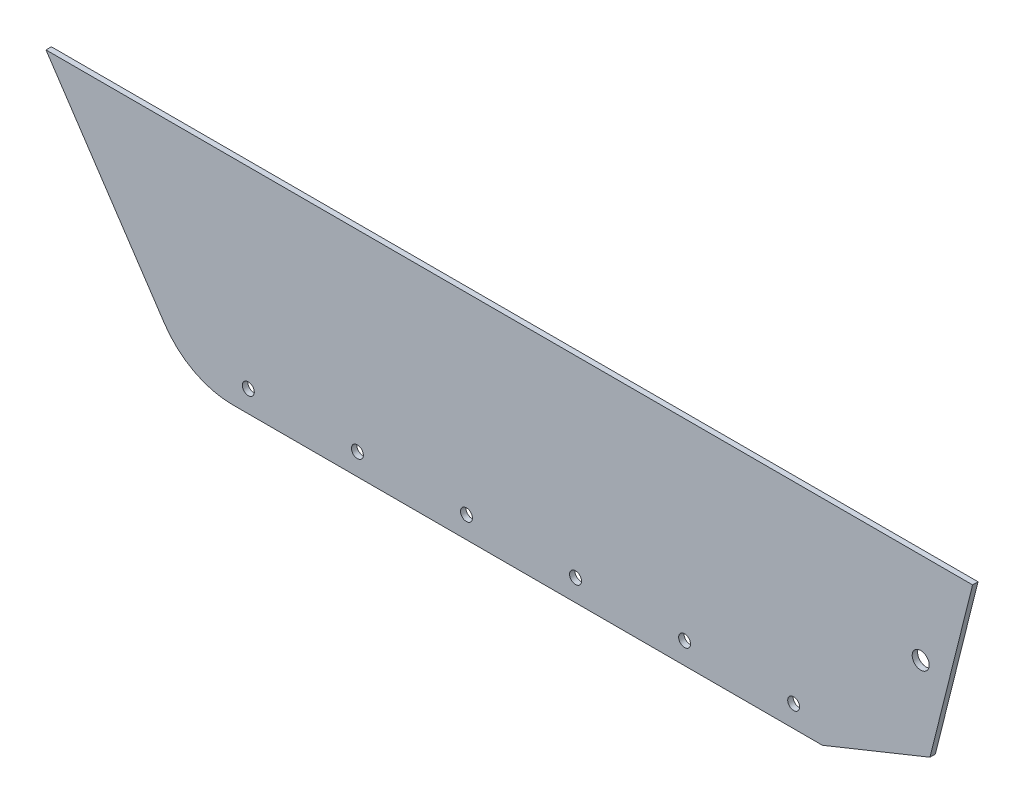
SolidWorks part; units mm, degrees
material "5052-H34"
ref_plane "Front Plane" through (0, 0, 0) normal (0, 0, 1) x (1, 0, 0)
ref_plane "Top Plane" through (0, 0, 0) normal (0, 1, 0) x (1, 0, 0)
ref_plane "Right Plane" through (0, 0, 0) normal (1, 0, 0) x (0, 0, -1)
sketch "Sketch1" plane through (0, 0, 0) normal (0, 0, 1) x (1, 0, 0)
  line L6 (-98.8794, 3.851) -> (-31.8794, -96.649)
  line L7 (428.1206, 28.9396) -> (403.1206, -71.149)
  line L9 (403.1206, -71.149) -> (366, -96.649)
  line L10 (-31.8794, -96.649) -> (366, -96.649)
  line L12 (-98.8794, 3.851) -> (-115.6052, 28.9396)
  line L13 (-115.6052, 28.9396) -> (428.1206, 28.9396)
  circle A0 centre (3.1206, -83.899) radius 3.5
  circle A1 centre (67.1206, -83.899) radius 3.5
  circle A2 centre (131.1206, -83.899) radius 3.5
  circle A3 centre (195.1206, -83.899) radius 3.5
  circle A4 centre (259.1206, -83.899) radius 3.5
  circle A5 centre (323.1206, -83.899) radius 3.5
  point P0 (-48.8794, -71.149)
  point P2 (-31.8794, -96.649)
  point P8 (48, -83.899)
  point P9 (403.1206, -71.149)
  dimension "D2" = 64
  dimension "D4" = 64
  dimension "D14" = 7
  dimension "D1" = 25.5
  dimension "D3" = 75
  dimension "D5" = 25
  dimension "D6" = 80
  dimension "D7" = 527
  dimension "D8" = 180
  dimension "D9" = 64
  dimension "D10" = 64
  dimension "D11" = 64
  dimension "D12" = 123.69
  dimension "D13" = 12.75
  dimension "D15" = 366
  dimension "D16" = 115.6052
extrude "Boss-Extrude1" add sketch "Sketch1" along normal blind 3.175 contours L12 L13 L7 L9 L10 L6
extrude "Cut-Extrude1" cut sketch "Sketch1<4>" along normal through all contours A0 | A1 | A2 | A3 | A4 | A5 region at (3.1206, -83.899, 0)
sketch "Sketch1<4>" plane through (0, 0, 0) normal (0, 0, 1) x (1, 0, 0) same geometry as "Sketch1"
sketch "Sketch2" plane through (0, 0, 0) normal (0, 0, -1) x (-1, 0, 0)
  circle A0 centre (-291.1206, -83.899) radius 6.5
  circle A2 centre (-241.5603, -124.3932) radius 6.5
  circle A3 centre (-192, -83.899) radius 6.5
  circle A4 centre (-128, -83.899) radius 6.5
  circle A5 centre (-64, -83.899) radius 6.5
  circle A6 centre (0, -83.899) radius 6.5
  dimension "D2" = 0
  dimension "D3" = 64
  dimension "D4" = 64
  dimension "D5" = 64
  dimension "D6" = 64
  dimension "D7" = 64
  dimension "D8" = 13
  dimension "D1" = 32
sketch "Sketch5" plane through (0, 0, 0) normal (0, 0, -1) x (-1, 0, 0)
  line L0 (48.8794, -71.149) -> (-14.2353, -96.649)
  line L1 (31.8794, -96.649) -> (-366, -96.649) construction
  line L2 (-14.2353, -96.649) -> (31.8794, -96.649)
  line L3 (31.8794, -96.649) -> (48.8794, -71.149)
  line L6 (-366, -96.649) -> (-403.1206, -71.149)
  line L7 (-403.1206, -71.149) -> (-352, -71.149)
  line L9 (-352, -71.149) -> (-326.5, -96.649)
  line L11 (-366, -96.649) -> (-326.5, -96.649)
  dimension "D1" = 22
  dimension "D2" = 45
extrude "Cut-Extrude2" [suppressed] cut sketch "Sketch5" against normal up to next
sketch "Sketch6" plane through (0, 0, 3.175) normal (0, 0, 1) x (1, 0, 0)
  line L0 (-48.8794, -71.149) -> (14.2353, -96.649)
  line L1 (-31.8794, -96.649) -> (366, -96.649) construction
  line L2 (14.2353, -96.649) -> (-31.8794, -96.649)
  line L3 (-31.8794, -96.649) -> (-48.8794, -71.149)
  dimension "D1" = 158
fillet "Fillet1" radius 48 1 edges at (-31.8794, -96.649, 1.5875)
sketch "Sketch7" plane through (0, 0, 3.175) normal (0, 0, 1) x (1, 0, 0)
  line L0 (403.1206, -71.149) -> (340.0059, -96.649)
  line L1 (-31.8794, -96.649) -> (366, -96.649) construction
  line L2 (340.0059, -96.649) -> (366, -96.649)
  line L3 (366, -96.649) -> (403.1206, -71.149)
  dimension "D1" = 22
extrude "Cut-Extrude3" cut sketch "Sketch7" against normal blind 10
sketch "Sketch9" plane through (0, 0, 0) normal (0, 0, -1) x (-1, 0, 0)
  line L0 (-403.1206, -71.149) -> (48.8794, -71.149)
  line L1 (48.8794, -71.149) -> (48.8794, -114.9143)
  line L2 (48.8794, -114.9143) -> (-403.1206, -114.9143)
  line L3 (-403.1206, -114.9143) -> (-403.1206, -71.149)
sketch "Sketch11" plane through (0, 0, 0) normal (0, 0, -1) x (-1, 0, 0)
  circle A0 centre (-397.6786, -24.6104) radius 5
extrude "Cut-Extrude5" cut sketch "Sketch11" against normal up to next
sketch "Sketch13" plane through (0, 0, 3.175) normal (0, 0, 1) x (1, 0, 0)
  line L0 (-115.6052, 28.9396) -> (428.1206, 28.9396) construction
  circle A0 centre (397.6786, -24.6104) radius 5 construction
  circle A1 centre (397.6786, -24.6104) radius 5
  circle A2 centre (-70.6052, -24.6104) radius 3
  dimension "D1" = 45
  dimension "D3" = 6
  dimension "D2" = 53.55
